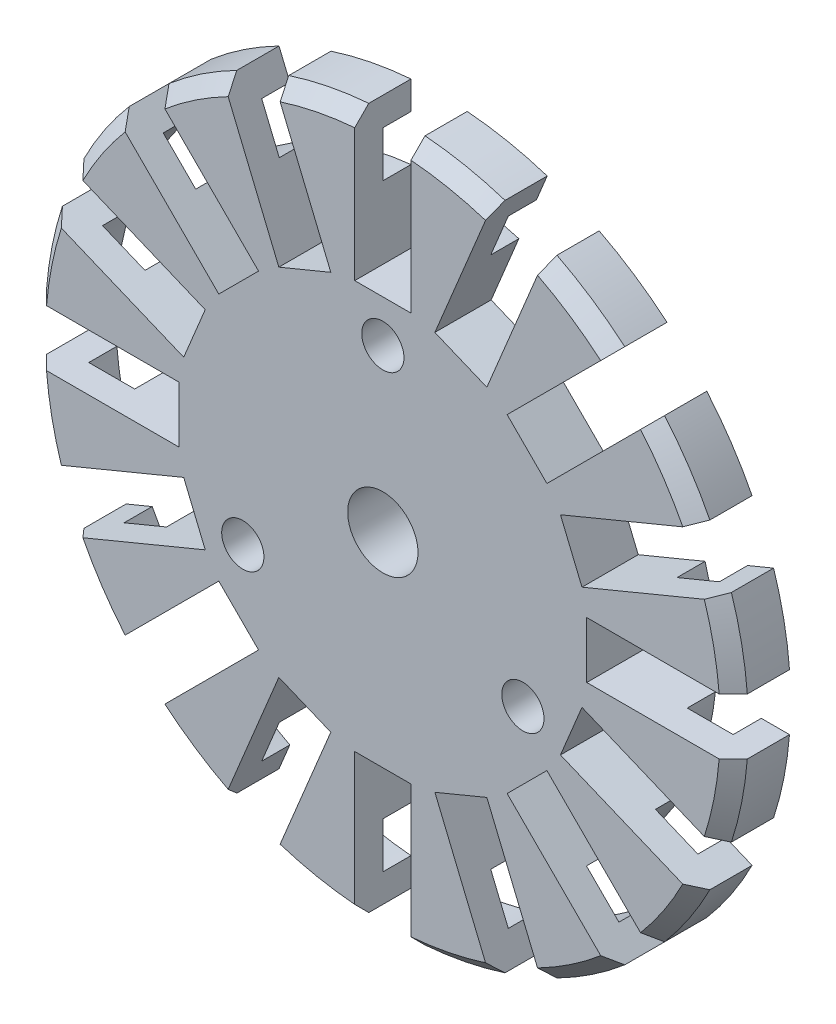
SolidWorks part; units mm, degrees
material "6061 Alloy"
ref_plane "Plano frontal" through (0, 0, 0) normal (0, 0, 1) x (1, 0, 0)
ref_plane "Plano superior" through (0, 0, 0) normal (0, 1, 0) x (1, 0, 0)
ref_plane "Plano direito" through (0, 0, 0) normal (1, 0, 0) x (0, 0, -1)
sketch "Esboço1" plane through (0, 0, 0) normal (0, 0, 1) x (1, 0, 0)
  circle A0 centre (0, 0) radius 25
extrude "Extrusão1" add sketch "Esboço1" along normal blind 4
sketch "Esboço2" plane through (0, 0, 4) normal (0, 0, 1) x (1, 0, 0)
  line L1 (0, 14.5) -> (2, 14.5)
  line L2 (2, 14.5) -> (2, 29.5)
  line L3 (2, 29.5) -> (-2, 29.5)
  line L4 (-2, 29.5) -> (-2, 14.5)
  line L5 (-2, 14.5) -> (0, 14.5)
extrude "Extrusão2" add sketch "Esboço2" against normal blind 5 and the other way blind 1 separate body
chamfer "Chanfro1" distance 1 angle 45 1 edges at (25, 0, 4)
ref_axis "Eixo1" through (0, 0, 22.4011) along (0, 0, -1)
pattern_circular "CirPattern1" count 16 over 360 about axis through (0, 0, 22.4011) along (0, 0, -1) of bodies 102
combine bodies "Combinar1" operation type subtract main body 101 bodies to subtract 103 102 117 116 115 114 113 112 111 110 109 108 107 106 105 104
sketch "Esboço5" plane through (0, 0, 4) normal (0, 0, 1) x (1, 0, 0)
  circle A0 centre (0, 11.5) radius 1.5
  circle A1 centre (9.9593, -5.75) radius 1.5
  circle A2 centre (-9.9593, -5.75) radius 1.5
  circle A3 centre (0, 0) radius 2.5
extrude "Corte-extrusão2" cut sketch "Esboço5" against normal through all
sketch "Esboço8" plane through (0, 0, 0) normal (0, 0, -1) x (-1, 0, 0)
  circle A1 centre (0, 0) radius 23
  circle A2 centre (0, 0) radius 19.75
extrude "Corte-extrusão4" cut sketch "Esboço8" against normal blind 2
